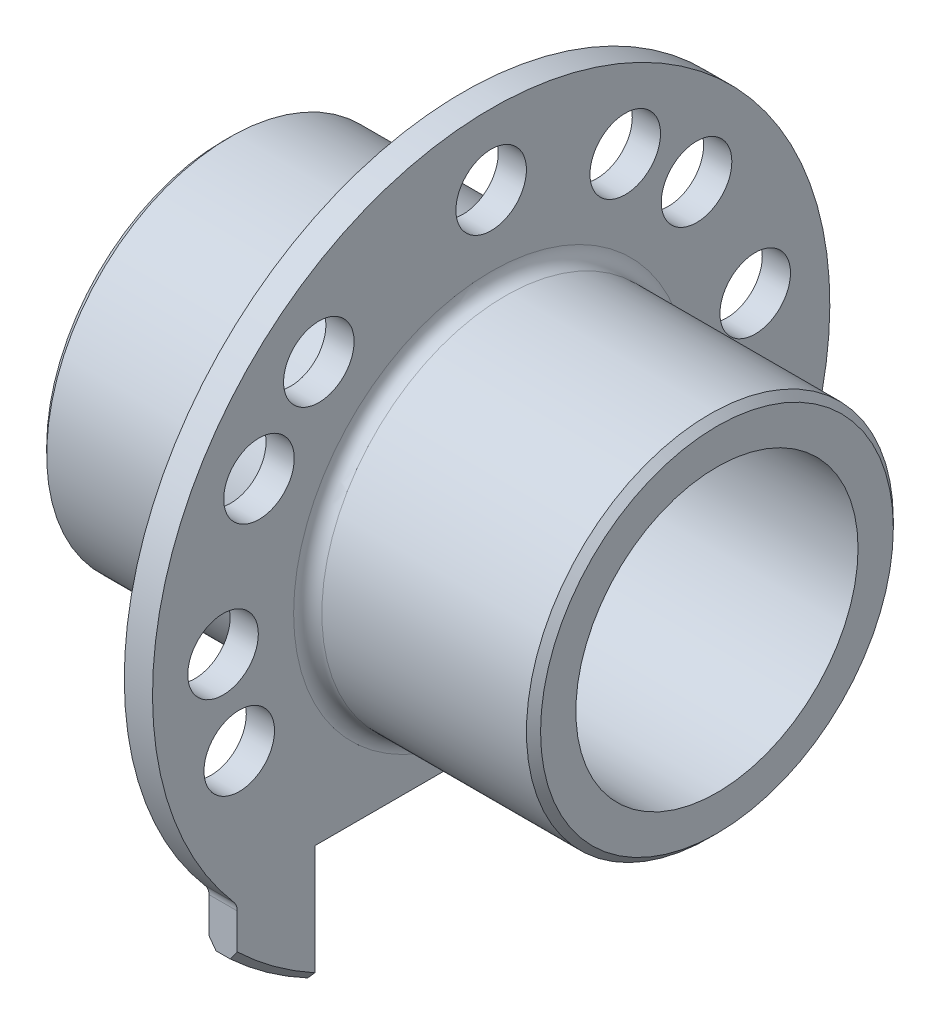
SolidWorks part; units mm, degrees
material "1.7218 (25CrMo4)"
ref_plane "Płaszczyzna XY" through (0, 0, 0) normal (0, 0, 1) x (1, 0, 0)
ref_plane "Płaszczyzna XZ" through (0, 0, 0) normal (0, 1, 0) x (1, 0, 0)
ref_plane "Płaszczyzna YZ" through (0, 0, 0) normal (1, 0, 0) x (0, 0, -1)
sketch "Sketch1" plane through (0, 0, 0) normal (1, 0, 0) x (0, 0, -1)
  circle A1 centre (0, 0) radius 13
  dimension "D2" = 26
extrude "Boss-Extrude1" add sketch "Sketch1" along normal blind 17 contours A1 region at (0, 0, 0)
sketch "Sketch2" plane through (0, 0, 0) normal (1, 0, 0) x (0, 0, -1)
  circle A0 centre (0, 0) radius 26.5
  dimension "D1" = 53
extrude "Boss-Extrude2" add sketch "Sketch2" along normal mid plane 2
sketch "Sketch3" plane through (0, 0, 0) normal (1, 0, 0) x (0, 0, -1)
  circle A0 centre (0, 0) radius 10
  dimension "D1" = 20
chamfer "Chamfer1" distance 0.5 angle 45 3 edges at (17, 0, -13) (1, 0, -26.5) (-1, 0, -26.5)
sketch "Sketch4" plane through (0, 0, 0) normal (1, 0, 0) x (0, 0, -1)
  line L0 (-19, 0) -> (22.0522, 0) construction
  line L1 (0, 19) -> (0, 0) construction
  line L2 (17.2198, -8.0297) -> (0, 0) construction
  line L3 (0, 0) -> (14.5548, 12.213) construction
  line L4 (0, 0) -> (-17.8542, -6.4984) construction
  line L5 (0, 0) -> (-16.4545, 9.5) construction
  line L6 (0, 0) -> (22.0285, 3.8842) construction
  line L7 (0, 0) -> (-12.213, 14.5548) construction
  line L8 (0, 0) -> (9.5, 16.4545) construction
  circle A4 centre (17.2198, -8.0297) radius 2.5
  circle A8 centre (-19, 0) radius 2.5
  circle A11 centre (14.5548, 12.213) radius 2.5
  circle A12 centre (0, 0) radius 19 construction
  circle A13 centre (0, 19) radius 2.5
  circle A14 centre (-17.8542, -6.4984) radius 2.5
  circle A15 centre (-16.4545, 9.5) radius 2.5
  circle A16 centre (18.7113, 3.2993) radius 2.5
  circle A17 centre (-12.213, 14.5548) radius 2.5
  circle A18 centre (9.5, 16.4545) radius 2.5
  dimension "D2" = 40
  dimension "D4" = 5
  dimension "D6" = 30
  dimension "D3" = 20
  dimension "D5" = 5
  dimension "D7" = 5
  dimension "D8" = 5
  dimension "D9" = 5
  dimension "D12" = 60
  dimension "D13" = 5
  dimension "D1" = 25
  dimension "D10" = 10
  dimension "D11" = 50
extrude "Wytnij-wyciągnięcie1" cut sketch "Sketch4" along normal through all both and the other way through all
ref_plane "Płaszczyzna1" through (-1, 0, 0) normal (-1, 0, 0) x (0, 0, 1)
sketch "Szkic4" plane through (-1, 0, 0) normal (-1, 0, 0) x (0, 0, 1)
  line L4 (18, -15.8745) -> (18, -28.4057)
  line L5 (-18, -15.8745) -> (-18, -25.4645)
  line L6 (18, -28.4057) -> (34.5626, -28.4057)
  line L7 (34.5626, -28.4057) -> (34.5626, 27.9159)
  line L8 (34.5626, 27.9159) -> (-37.9049, 28.9794)
  line L9 (-37.9049, 28.9794) -> (-37.9049, -27.4602)
  line L10 (-37.9049, -27.4602) -> (-18, -25.4645)
  arc A0 (18, -15.8745) -> (-18, -15.8745) centre (0, 0) ccw
extrude "Dodanie-wyciągnięcie1" add sketch "Sketch1<3>" against normal blind 18
sketch "Sketch1<3>" plane through (0, 0, 0) normal (1, 0, 0) x (0, 0, -1) same geometry as "Sketch1"
sketch "Szkic5" plane through (17, 0, 0) normal (1, 0, 0) x (0, 0, -1)
  circle A0 centre (0, 0) radius 10
extrude "Wytnij-wyciągnięcie2" cut sketch "Szkic5" against normal blind 40
extrude "Wytnij-wyciągnięcie3" cut sketch "Szkic4" against normal blind 40
chamfer "Sfazowanie1" distance 0.5 angle 45 1 edges at (-18, 0, -13)
fillet "Zaokrąglenie1" radius 1 2 edges at (1, 0, -13) (-1, 0, -13)
sketch "Szkic7" plane through (-1, 0, 0) normal (-1, 0, 0) x (0, 0, 1)
  line L0 (-12.5, -15) -> (12.5, -15)
  line L1 (12.5, -15) -> (12.5, -33.2508)
  line L2 (-12.5, -15) -> (-12.5, -33.2508)
  line L3 (12.5, -33.2508) -> (-12.5, -33.2508)
  dimension "D1" = 25
  dimension "D2" = 15
  dimension "D3" = 12.5
extrude "Wytnij-wyciągnięcie4" cut sketch "Szkic7" against normal blind 10
fillet "Zaokrąglenie2" radius 1 2 edges at (0, -15.8745, -18) (0, -15.8745, 18)
